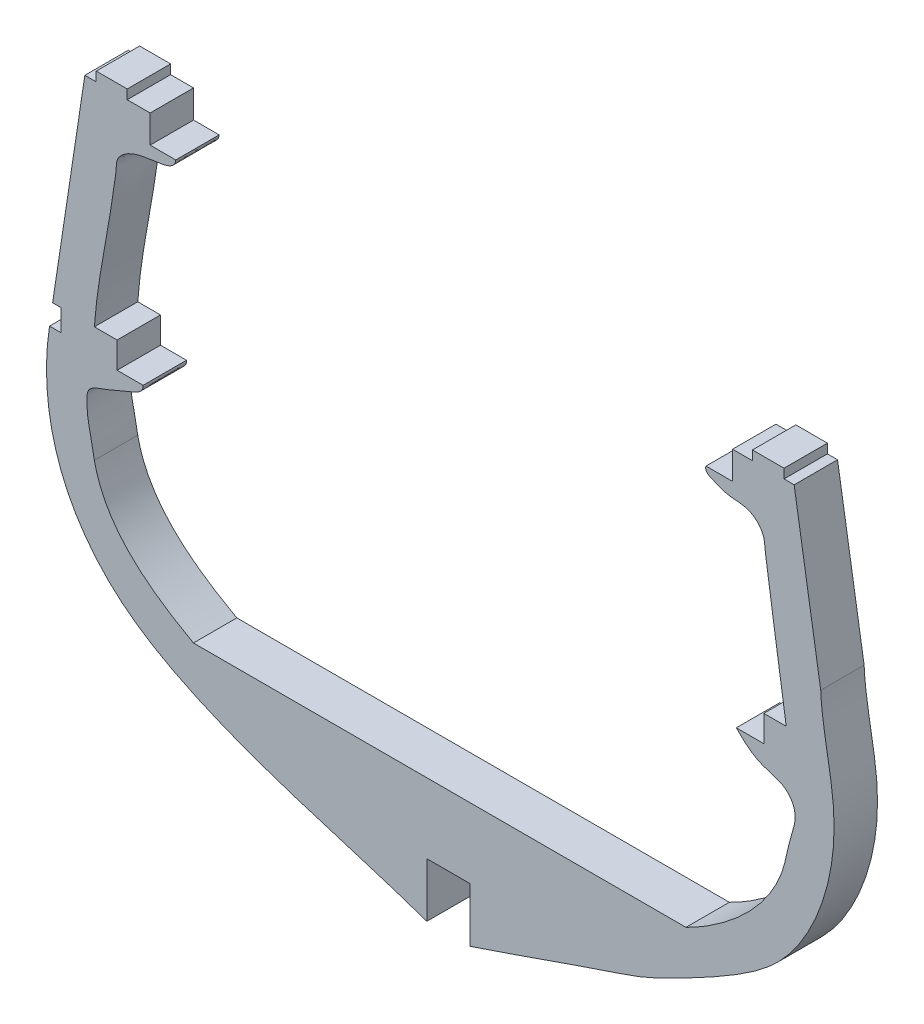
SolidWorks part; units mm, degrees
ref_plane "前视基准面" through (0, 0, 0) normal (0, 0, 1) x (1, 0, 0)
ref_plane "上视基准面" through (0, 0, 0) normal (0, 1, 0) x (1, 0, 0)
ref_plane "右视基准面" through (0, 0, 0) normal (1, 0, 0) x (0, 0, -1)
other "Configuration Table"
sketch "草图1" plane through (0, 0, 0) normal (0, 0, 1) x (1, 0, 0)
  line L0 (376.6667, 613.5) -> (1883.3333, 613.5) construction
  line L1 (2023.8565, -283.355) -> (2023.8565, -293.355)
  line L30 (2063.6269, -270.439) -> (1972.85, -270.439)
  line L32 (2023.8565, -283.355) -> (2015.8548, -283.355)
  line L33 (2015.8548, -283.355) -> (2015.8729, -293.355)
  line L34 (2083.5638, -189.8347) -> (2081.7002, -189.8347)
  line L35 (2081.7002, -189.8347) -> (2081.7002, -188.1152)
  line L36 (2081.7002, -188.1152) -> (2075.8765, -188.1152)
  line L37 (2075.8765, -188.1152) -> (2075.8765, -189.8347)
  line L38 (2075.8765, -189.8347) -> (2072.2076, -189.8347)
  line L39 (2072.2076, -189.8347) -> (2072.2076, -194.9685)
  line L40 (2072.2076, -194.9685) -> (2067.3157, -194.9685)
  line L41 (2082.1078, -229.114) -> (2077.973, -229.114)
  line L42 (2077.973, -229.114) -> (2077.973, -233.9476)
  line L43 (2077.973, -233.9476) -> (2072.9064, -233.9476)
  line L44 (1946.8988, -229.114) -> (1948.4602, -229.114)
  line L45 (1948.4602, -229.114) -> (1948.4602, -233.1217)
  line L46 (1948.4602, -233.1217) -> (1946.3276, -233.1217)
  line L47 (1954.5915, -229.114) -> (1958.7805, -229.114)
  line L48 (1958.7805, -229.114) -> (1958.7805, -233.9476)
  line L49 (1958.7805, -233.9476) -> (1963.5789, -233.9476)
  line L50 (1952.8397, -189.8347) -> (1954.9342, -189.8347)
  line L51 (1954.9342, -189.8347) -> (1954.9342, -188.1152)
  line L52 (1954.9342, -188.1152) -> (1960.6466, -188.1152)
  line L53 (1960.6466, -188.1152) -> (1960.6466, -189.8347)
  line L54 (1960.6466, -189.8347) -> (1964.8737, -189.8347)
  line L55 (1964.8737, -189.8347) -> (1964.8737, -194.9685)
  line L56 (1964.8737, -194.9685) -> (1969.596, -194.9685)
  spline S8 degree 3 poles (1969.596, -194.9685) (1969.4798, -196.2695) (1967.4319, -196.9189) (1964.422, -197.2697) (1961.3628, -197.7861) (1958.6005, -199.772) (1958.6621, -201.8869) (1958.268, -204.5676) (1956.9752, -213.6231) (1955.0652, -222.1681) (1954.5915, -229.114) knots 0 0 0 0 0.079837 0.134651 0.222997 0.305779 0.343473 0.36885 0.501792 1 1 1 1
  spline S9 degree 1 poles (1952.8397, -189.8347) (1946.8988, -229.114) knots 0 0 1 1
  spline S10 degree 3 poles (1946.3276, -233.1217) (1945.0823, -241.0317) (1946.3828, -255.1158) (1957.7283, -270.2499) (1980.4393, -283.6544) (2000.9567, -288.122) (2015.8729, -293.355) knots 0 0 0 0 0.2359 0.393499 0.534821 1 1 1 1
  spline S11 degree 3 poles (1972.85, -270.439) (1964.8636, -266.0123) (1956.6104, -260.1441) (1954.5915, -250.4094) knots 0 0 0 0 1 1 1 1
  spline S12 degree 3 poles (1963.5789, -233.9476) (1963.6575, -234.8355) (1962.2396, -235.8693) (1959.4654, -236.7581) (1956.7342, -238.1766) (1953.3159, -239.1365) (1953.0176, -244.1911) (1954.0662, -247.0558) (1954.5915, -250.4094) knots 0 0 0 0 0.102963 0.208523 0.386782 0.529425 0.602819 1 1 1 1
  spline S13 degree 1 poles (2083.5638, -189.8347) (2088.4628, -220.1655) knots 0 0 1 1
  spline S14 degree 3 poles (2088.4628, -220.1655) (2088.6979, -226.2098) (2091.4724, -235.5935) (2090.3735, -252.1559) (2084.0186, -265.6786) (2072.1109, -274.194) (2053.7585, -283.6307) (2054.7336, -282.529) (2027.1196, -292.3286) (2023.8565, -293.355) knots 0 0 0 0 0.157382 0.247757 0.428753 0.514164 0.636987 0.881281 0.970187 0.970187 0.970187 0.970187
  spline S15 degree 3 poles (2067.3157, -194.9685) (2067.0239, -195.9441) (2069.0389, -196.7117) (2071.6729, -197.8236) (2075.4571, -197.4998) (2078.047, -200.2609) (2078.1833, -202.7809) (2079.5605, -212.1145) (2080.8331, -220.9488) (2082.1078, -229.114) knots 0 0 0 0 0.060524 0.124111 0.219635 0.316289 0.355323 0.400899 1 1 1 1
  spline S16 degree 3 poles (2063.6269, -270.439) (2071.1917, -266.6984) (2080.7453, -258.7449) (2082.6269, -246.7951) (2084.4732, -242.4005) (2081.7705, -238.3356) (2076.9795, -237.8043) (2074.2153, -235.324) (2072.9064, -233.9476) knots 0 0 0 0 0.528587 0.619056 0.732797 0.785422 0.885179 1 1 1 1
  dimension "D1" = 8.0018
  dimension "D2" = 10
extrude "凸台-拉伸1" add sketch "草图1" along normal blind 8
